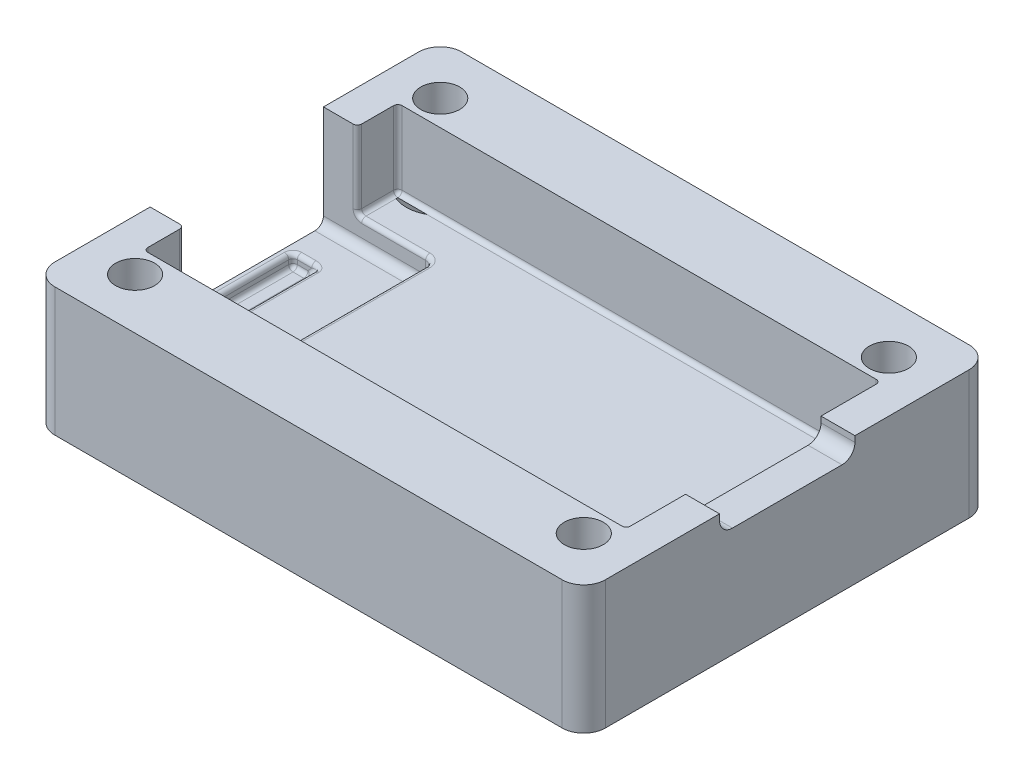
SolidWorks part; units mm, degrees
ref_plane "Front Plane" through (0, 0, 0) normal (0, 0, 1) x (1, 0, 0)
ref_plane "Top Plane" through (0, 0, 0) normal (0, 1, 0) x (1, 0, 0)
ref_plane "Right Plane" through (0, 0, 0) normal (1, 0, 0) x (0, 0, -1)
sketch "Sketch1" plane through (0, 0, 0) normal (0, 1, 0) x (1, 0, 0)
  line L0 (58.9293, 5.9568) -> (58.9293, -15.4892) construction
  line L1 (58.9293, 7.2268) -> (26.4813, 7.2268)
  line L2 (58.9293, 7.2268) -> (58.9293, -16.7592)
  line L3 (58.9293, -16.7592) -> (26.4813, -16.7592)
  line L4 (26.4813, 7.2268) -> (26.4813, -16.7592)
  line L5 (58.9293, 7.2268) -> (26.4813, -16.7592) construction
  line L6 (58.9293, -16.7592) -> (26.4813, 7.2268) construction
  line L7 (27.7513, 7.2268) -> (57.6593, 7.2268) construction
  line L8 (26.4813, -15.4892) -> (26.4813, 5.9568) construction
  line L9 (57.6593, -16.7592) -> (27.7513, -16.7592) construction
  point P0 (0, 0)
extrude "Boss-Extrude1" add sketch "Sketch1" along normal blind 7.572
sketch "Sketch3" plane through (0, 7.572, 0) normal (0, 1, 0) x (1, 0, 0)
  line L1 (56.9293, -12.2592) -> (28.4813, -12.2592)
  line L2 (56.9293, -12.2592) -> (56.9293, 2.7268)
  line L3 (56.9293, 2.7268) -> (28.4813, 2.7268)
  line L4 (28.4813, -12.2592) -> (28.4813, 2.7268)
  line L5 (56.9293, -12.2592) -> (28.4813, 2.7268) construction
  line L6 (56.9293, 2.7268) -> (28.4813, -12.2592) construction
  line L8 (56.9293, 2.4728) -> (56.9293, -0.7748) construction
  line L9 (28.7353, 2.7268) -> (56.6753, 2.7268) construction
  line L10 (56.6753, -12.2592) -> (28.7353, -12.2592) construction
  line L11 (28.4813, -12.0052) -> (28.4813, -9.8753) construction
  point P0 (0, 0)
extrude "Cut-Extrude1" cut sketch "Sketch3" against normal blind 4.572
fillet "Fillet1" radius 1.27 4 edges at (26.4813, 3.786, -7.2268) (58.9293, 3.786, -7.2268) (26.4813, 3.786, 16.7592) (58.9293, 3.786, 16.7592)
fillet "Fillet2" radius 0.254 4 edges at (56.9293, 5.286, -2.7268) (56.9293, 5.286, 12.2592) (28.4813, 5.286, 12.2592) (28.4813, 5.286, -2.7268)
fillet "Fillet3" radius 0.254 8 edges at (56.8549, 3, 12.1848) (42.7053, 3, 12.2592) (28.5557, 3, 12.1848) (28.4813, 3, 4.7662) (28.5557, 3, -2.6524) (42.7053, 3, -2.7268) (56.8549, 3, -2.6524) (56.9293, 3, 4.7662)
sketch "Sketch5" plane through (26.4813, 0, 0) normal (-1, 0, 0) x (0, 0, 1)
  line L0 (-5.9568, 7.572) -> (15.4892, 7.572) construction
  line L1 (9.8753, 7.572) -> (-0.3429, 7.572) construction
  line L2 (9.8753, 7.572) -> (9.8753, 1.5)
  line L3 (9.8753, 1.5) -> (-0.3429, 1.5)
  line L4 (-0.3429, 7.572) -> (-0.3429, 1.5)
  line L5 (-5.9568, 0) -> (15.4892, 0) construction
  line L11 (-0.3429, 7.572) -> (9.8753, 7.572)
  line L15 (-0.3429, 7.572) -> (9.8753, 7.572)
  line L16 (-0.3429, 8.072) -> (-0.3429, 7.572)
  line L17 (9.8753, 8.072) -> (-0.3429, 8.072)
  line L18 (9.8753, 7.572) -> (9.8753, 8.072)
  line L19 (-0.3429, 7.572) -> (9.8753, 7.572) construction
  line L20 (-0.3429, 8.072) -> (-0.3429, 7.572) construction
  line L21 (9.8753, 8.072) -> (-0.3429, 8.072) construction
  line L22 (9.8753, 7.572) -> (9.8753, 8.072) construction
  point P8 (4.7662, 7.572)
  point P9 (4.7662, 0)
  dimension "D1" = 1.5
  dimension "D2" = 0
extrude "Cut-Extrude3" cut sketch "Sketch5" against normal up to surface (6.5278 mm away)
fillet "Fillet4" radius 0.508 5 edges at (29.7452, 1.5, -0.3429) (29.7452, 1.5, 9.8753) (33.0092, 1.5, 4.7662) (33.0092, 2.25, 9.8753) (33.0092, 2.25, -0.3429)
ref_plane "Plane1" through (56.6753, 3, -2.4728) normal (0, 0, -1) x (-1, 0, 0)
sketch "Sketch7" plane through (58.9293, 0, 0) normal (1, 0, 0) x (0, 0, -1)
  line L0 (5.9568, 7.572) -> (-0.7748, 7.572) construction
  line L1 (-0.7748, 7.572) -> (-8.7576, 7.572)
  line L2 (-0.7748, 7.572) -> (-0.7748, 6.4638)
  line L3 (-0.7748, 6.4638) -> (-8.7576, 6.4638)
  line L4 (-8.7576, 7.572) -> (-8.7576, 6.4638)
  line L5 (-15.4892, 0) -> (5.9568, 0) construction
  point P6 (-4.7662, 6.4638)
  point P9 (-4.7662, 0)
extrude "Cut-Extrude4" cut sketch "Sketch7" against normal up to surface (2 mm away) up to face at (56.9293, 5.413, 4.7662)
fillet "Fillet5" radius 0.762 2 edges at (57.9293, 6.4638, 8.7576) (57.9293, 6.4638, 0.7748)
sketch "Sketch8" plane through (0, 0, 0) normal (0, -1, 0) x (-1, 0, 0)
  line L0 (-26.4813, 5.9568) -> (-26.4813, -15.4892) construction
  line L16 (-58.9293, -16.7592) -> (-26.4813, -16.7592) construction
  line L17 (-58.9293, -16.7592) -> (-58.9293, 7.2268) construction
  line L18 (-58.9293, 7.2268) -> (-26.4813, 7.2268) construction
  line L19 (-26.4813, -16.7592) -> (-26.4813, 7.2268) construction
  line L20 (-57.6593, 7.2268) -> (-27.7513, 7.2268) construction
  line L21 (-58.9293, -15.4892) -> (-58.9293, 5.9568) construction
  line L22 (-27.7513, -16.7592) -> (-57.6593, -16.7592) construction
  line L23 (-57.9293, 6.2268) -> (-27.4813, 6.2268) construction
  line L24 (-27.4813, -15.7592) -> (-27.4813, 6.2268) construction
  line L25 (-57.9293, -15.7592) -> (-27.4813, -15.7592) construction
  line L26 (-57.9293, -15.7592) -> (-57.9293, 6.2268) construction
  circle A0 centre (-55.9293, 4.2268) radius 2
  circle A1 centre (-29.4813, 4.2268) radius 2
  circle A2 centre (-29.4813, -13.7592) radius 2
  circle A3 centre (-55.9293, -13.7592) radius 2
  dimension "D1" = 4
  dimension "D2" = 1
extrude "Cut-Extrude5" cut sketch "Sketch8" against normal blind 3
sketch "Sketch9" plane through (0, 0, 0) normal (0, -1, 0) x (-1, 0, 0)
  circle A0 centre (-55.9293, 4.2268) radius 1.15
  circle A2 centre (-29.4813, 4.2268) radius 1.15
  circle A3 centre (-29.4813, -13.7592) radius 1.15
  circle A4 centre (-55.9293, -13.7592) radius 1.15
  circle A8 centre (-55.9293, -13.7592) radius 2 construction
  circle A9 centre (-55.9293, 4.2268) radius 2 construction
  circle A10 centre (-29.4813, 4.2268) radius 2 construction
  circle A11 centre (-29.4813, -13.7592) radius 2 construction
  dimension "D1" = 2.3
extrude "Cut-Extrude7" cut sketch "Sketch9" against normal through all
ref_plane "Plane2" through (0, 0, 7.4071) normal (0, 0, 1) x (1, 0, 0)
ref_plane "Plane3" through (0, 0, 1.9071) normal (0, 0, -1) x (-1, 0, 0)
sketch "Sketch10" plane through (0, 0, 7.4071) normal (0, 0, 1) x (1, 0, 0)
  line L0 (26.9369, 4.4275) -> (26.9369, 3.4275) construction
  line L1 (26.9369, 4.4275) -> (26.9369, 3.4275) construction
  line L2 (26.9369, 3.4275) -> (27.4369, 3.4275) construction
  line L3 (26.9369, 1.75) -> (28.8369, 1.75)
  line L4 (26.9369, 3.4275) -> (27.4369, 3.4275) construction
  line L5 (27.4369, 3.4275) -> (28.3369, 4.4275) construction
  line L6 (27.4369, 3.4275) -> (28.3369, 4.4275) construction
  line L7 (28.3369, 4.4275) -> (26.9369, 4.4275) construction
  line L12 (28.8369, 1.75) -> (27.9369, 0.75)
  line L13 (27.9369, 0.75) -> (26.9369, 0.75)
  line L14 (26.9369, 0.75) -> (26.9369, 1.75)
  line L15 (27.7513, 0) -> (57.6593, 0) construction
  line L16 (27.4369, 3.4275) -> (27.4369, 0.75) construction
  line L17 (27.7513, 0) -> (57.6593, 0) construction
  line L18 (28.3369, 4.4275) -> (28.3369, 1.75) construction
  point P11 (29.3439, 1.5)
  dimension "D1" = 0.75
  dimension "D2" = 0.5
extrude "Cut-Extrude8" cut sketch "Sketch10" against normal up to surface (5.5 mm away) up to plane "Plane3"
fillet "Fillet8" radius 0.254 9 edges at (28.4813, 5.413, 9.8753) (28.5557, 3.0744, 9.8753) (30.6182, 3, 9.8753) (32.8604, 3, 9.7265) (33.0092, 3, 4.7662) (32.8604, 3, -0.1941) (28.4813, 5.413, -0.3429) (28.5557, 3.0744, -0.3429) (30.6182, 3, -0.3429)
fillet "Fillet10" radius 0.254 12 edges at (27.7744, 1.5, 1.9071) (27.7744, 1.5, 7.4071) (26.9369, 1.125, 1.9071) (26.9369, 1.125, 7.4071) (26.9369, 1.5, 4.6571) (28.2744, 1.125, 1.9071) (28.6119, 1.5, 4.6571) (28.2744, 1.125, 7.4071) (27.4369, 0.75, 1.9071) (27.9369, 0.75, 4.6571) (27.4369, 0.75, 7.4071) (26.9369, 0.75, 4.6571)
